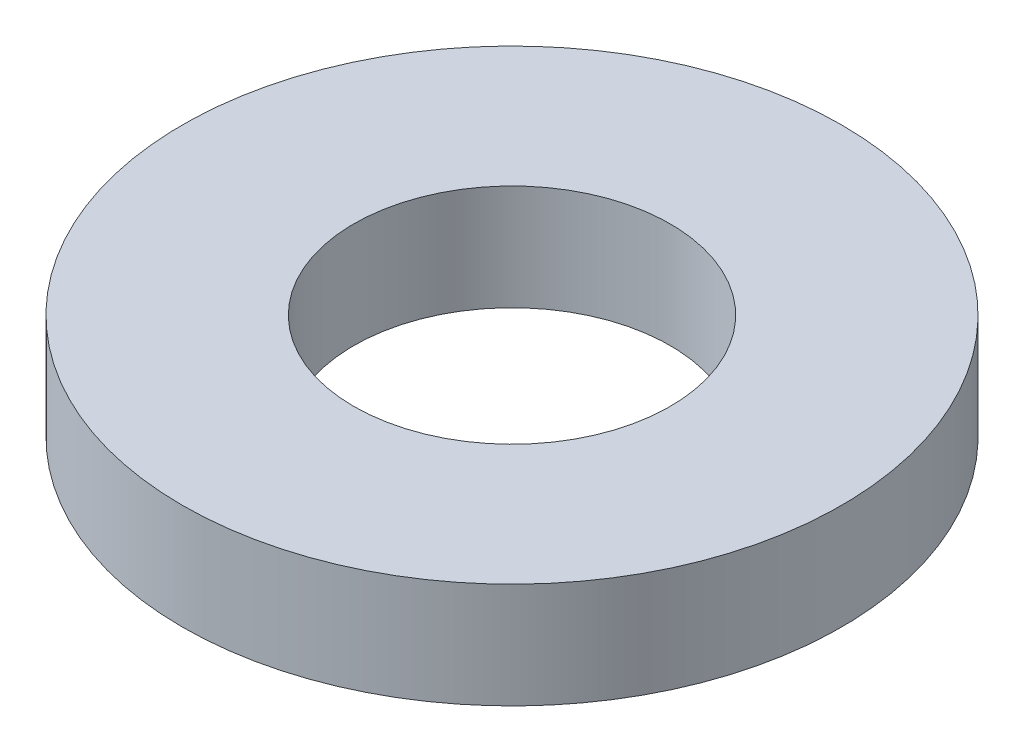
SolidWorks part; units mm, degrees
ref_plane "Front Plane" through (0, 0, 0) normal (0, 0, 1) x (1, 0, 0)
ref_plane "Top Plane" through (0, 0, 0) normal (0, 1, 0) x (1, 0, 0)
ref_plane "Right Plane" through (0, 0, 0) normal (1, 0, 0) x (0, 0, -1)
sketch "Sketch1" plane through (0, 0, 0) normal (0, 1, 0) x (1, 0, 0)
  circle A0 centre (0, 0) radius 62.5
  dimension "FLANGE_OD" = 125
extrude "Boss-Extrude1" add sketch "Sketch1" along normal blind 20
sketch "Sketch2" plane through (0, 0, 0) normal (0, 1, 0) x (1, 0, 0)
  circle A0 centre (0, 0) radius 30
  dimension "BORE_D" = 60
extrude "Cut-Extrude1" cut sketch "Sketch2" along normal through all
sketch "Sketch3" plane through (0, 20, 0) normal (0, 1, 0) x (1, 0, 0)
  circle A0 centre (0, 0) radius 22.6349 construction
  circle A1 centre (-22.6349, 0) radius 5.1315
  dimension "BOLT_D" = 10.263
  dimension "BOLT_PCD" = 45.2699
extrude "Cut-Extrude2" cut sketch "Sketch3" against normal blind 17.633 rebuild error yes
pattern_circular "CirPattern1" count 6 over 360 rebuild error yes
